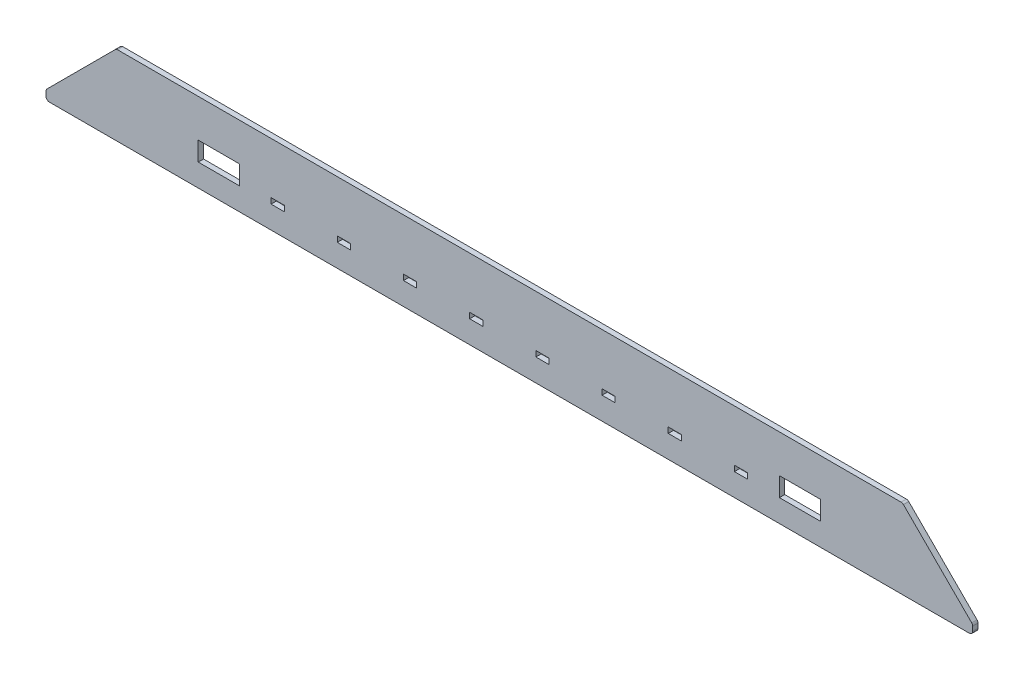
SolidWorks part; units mm, degrees
ref_plane "Front Plane" through (0, 0, 0) normal (0, 0, 1) x (1, 0, 0)
ref_plane "Top Plane" through (0, 0, 0) normal (0, 1, 0) x (1, 0, 0)
ref_plane "Right Plane" through (0, 0, 0) normal (1, 0, 0) x (0, 0, -1)
sketch "Sketch1" plane through (0, 0, 0) normal (0, 0, 1) x (1, 0, 0)
  line L0 (0, 2.7868) -> (21.2132, 24)
  line L1 (0, 0) -> (280, 0)
  line L2 (0, 0) -> (0, 24)
  line L3 (0, 24) -> (280, 24)
  line L4 (280, 0) -> (280, 24)
  line L5 (42, 0) -> (238, 0)
  line L6 (42, 0) -> (42, 11)
  line L7 (46, 15) -> (234, 15)
  line L8 (238, 0) -> (238, 11)
  line L9 (280, 2.7868) -> (258.7868, 24)
  arc A0 (234, 15) -> (238, 11) centre (234, 11) cw
  arc A1 (42, 11) -> (46, 15) centre (46, 11) cw
  dimension "D3" = 4
  dimension "D1" = 45
  dimension "D2" = 45
  dimension "D4" = 42
  dimension "D5" = 15
  dimension "D6" = 280
  dimension "D7" = 30
  dimension "D8" = 30
  dimension "D9" = 24
  dimension "D10" = 42
extrude "Boss-Extrude1" add sketch "Sketch1" along normal blind 1.6 contours L6 A1 L7 A0 L8 L1 L4 L9 L3 L0 L2 region at (140, 15.3044, 0)
fillet "Fillet1" radius 1 6 edges at (258.7868, 24, 0.8) (280, 0, 0.8) (280, 2.7868, 0.8) (0, 2.7868, 0.8) (0, 0, 0.8) (21.2132, 24, 0.8)
sketch "Sketch2" plane through (0, 0, 0) normal (0, 0, 1) x (1, 0, 0)
  line L0 (46, 15) -> (234, 15) construction
  line L5 (46, 6.8) -> (58.4, 6.8)
  line L6 (46, 6.8) -> (46, 12.55)
  line L7 (46, 12.55) -> (58.4, 12.55)
  line L8 (58.4, 6.8) -> (58.4, 12.55)
  line L45 (88.01, 6.8) -> (91.99, 6.8)
  line L46 (68.01, 6.8) -> (71.99, 6.8)
  line L47 (221.6, 6.8) -> (234, 6.8)
  line L48 (221.6, 6.8) -> (221.6, 12.55)
  line L49 (221.6, 12.55) -> (234, 12.55)
  line L50 (234, 6.8) -> (234, 12.55)
  line L51 (42, 0) -> (42, 11) construction
  line L52 (238, 0) -> (238, 11) construction
  line L53 (68.01, 6.8) -> (68.01, 8.5)
  line L54 (68.01, 8.5) -> (71.99, 8.5)
  line L55 (71.99, 6.8) -> (71.99, 8.5)
  line L56 (88.01, 6.8) -> (88.01, 8.5)
  line L57 (88.01, 8.5) -> (91.99, 8.5)
  line L58 (91.99, 6.8) -> (91.99, 8.5)
  line L59 (108.01, 6.8) -> (111.99, 6.8)
  line L60 (108.01, 6.8) -> (108.01, 8.5)
  line L61 (108.01, 8.5) -> (111.99, 8.5)
  line L62 (111.99, 6.8) -> (111.99, 8.5)
  line L63 (128.01, 6.8) -> (131.99, 6.8)
  line L64 (128.01, 6.8) -> (128.01, 8.5)
  line L65 (128.01, 8.5) -> (131.99, 8.5)
  line L66 (131.99, 6.8) -> (131.99, 8.5)
  line L67 (148.01, 6.8) -> (151.99, 6.8)
  line L68 (148.01, 6.8) -> (148.01, 8.5)
  line L69 (148.01, 8.5) -> (151.99, 8.5)
  line L70 (151.99, 6.8) -> (151.99, 8.5)
  line L71 (168.01, 6.8) -> (171.99, 6.8)
  line L72 (168.01, 6.8) -> (168.01, 8.5)
  line L73 (168.01, 8.5) -> (171.99, 8.5)
  line L74 (171.99, 6.8) -> (171.99, 8.5)
  line L75 (188.01, 6.8) -> (191.99, 6.8)
  line L76 (188.01, 6.8) -> (188.01, 8.5)
  line L77 (188.01, 8.5) -> (191.99, 8.5)
  line L78 (191.99, 6.8) -> (191.99, 8.5)
  line L79 (208.01, 6.8) -> (211.99, 6.8)
  line L80 (208.01, 6.8) -> (208.01, 8.5)
  line L81 (208.01, 8.5) -> (211.99, 8.5)
  line L82 (211.99, 6.8) -> (211.99, 8.5)
  line L83 (68.01, 6.8) -> (88.01, 6.8) construction
  line L84 (131.99, 6.8) -> (148.01, 6.8)
  line L85 (0, 0) -> (280, 0) construction
  point P10 (140, 6.8)
  point P49 (140, 15)
  dimension "D2" = 8
  dimension "D3" = 12.4
  dimension "D4" = 5.75
  dimension "D5" = 20
  dimension "D7" = 1.7
  dimension "D8" = 12.4
  dimension "D9" = 5.75
  dimension "D10" = 4
  dimension "D11" = 4
  dimension "D6" = 6.8
  dimension "D12" = 3.98
  dimension "D13" = 6.5
extrude "Boss-Extrude2" add sketch "Sketch1<3>" along normal blind 1.6 contours A1 L6 L1 L8 A0 L7 region at (140, 7.4845, 0)
sketch "Sketch1<3>" plane through (0, 0, 0) normal (0, 0, 1) x (1, 0, 0) same geometry as "Sketch1"
extrude "Cut-Extrude1" cut sketch "Sketch2" along normal through all both and the other way through all contours L5 L8 L7 L6 | L46 L55 L54 L53 | L45 L58 L57 L56 | L59 L62 L61 L60 | L67 L70 L69 L68 | L71 L74 L73 L72 | L75 L78 L77 L76 | L79 L82 L81 L80 | L47 L50 L49 L48 | L63 L66 L65 L64 region at (52.2, 9.675, 0) region at (90, 7.65, 0) region at (70, 7.65, 0) region at (227.8, 9.675, 0) region at (110, 7.65, 0) region at (130, 7.65, 0) region at (150, 7.65, 0) region at (170, 7.65, 0) region at (190, 7.65, 0) region at (210, 7.65, 0)
